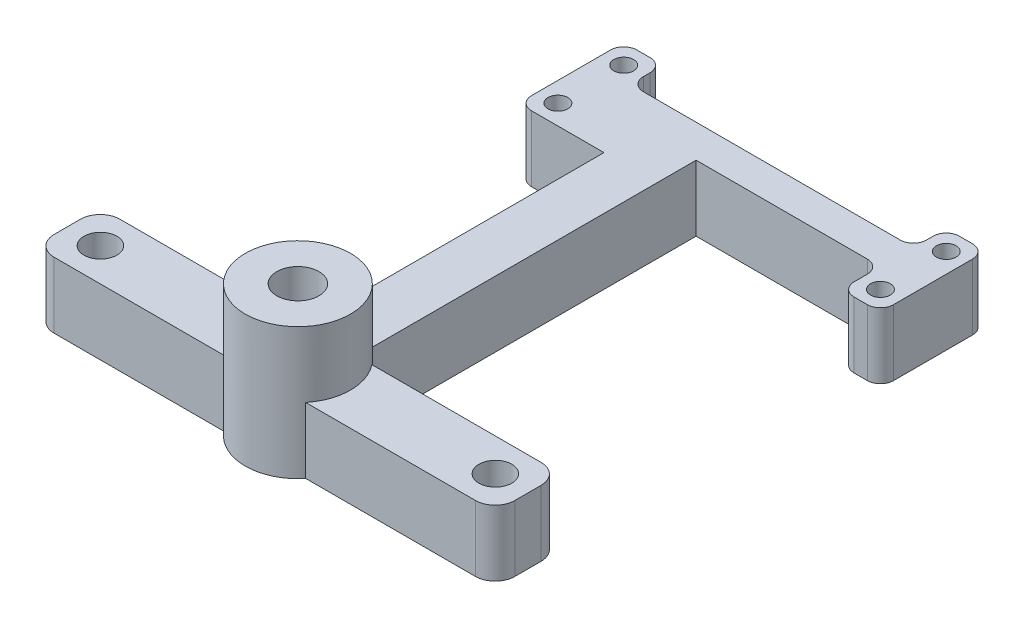
SolidWorks part; units mm, degrees
ref_plane "前视基准面" through (0, 0, 0) normal (0, 0, 1) x (1, 0, 0)
ref_plane "上视基准面" through (0, 0, 0) normal (0, 1, 0) x (1, 0, 0)
ref_plane "右视基准面" through (0, 0, 0) normal (1, 0, 0) x (0, 0, -1)
other "Configuration Table"
sketch "草图2" plane through (0, 0, 0) normal (0, 1, 0) x (1, 0, 0)
  line L1 (-4, -23) -> (4, -23)
  line L2 (-4, -23) -> (-4, -6)
  line L3 (-4, -6) -> (4, -6)
  line L4 (4, -23) -> (4, -6)
  line L5 (-4, -23) -> (4, -6) construction
  line L6 (-4, -6) -> (4, -23) construction
extrude "凸台-拉伸1" add sketch "草图2" along normal blind 10
sketch "草图4" plane through (0, 10, 0) normal (0, 1, 0) x (1, 0, 0)
  line L1 (-4, -23) -> (4, -23)
  line L4 (4, -23) -> (4, -61.5319)
  line L5 (-4, -23) -> (-4, -61.5319)
  line L11 (-4, -23) -> (4, -23) construction
  line L17 (-35, -61.5319) -> (-4, -61.5319)
  line L18 (-11.3444, -64.4193) -> (11.3444, -68.5807) construction
  line L20 (-11.3444, -84.9254) -> (11.3444, -48.0746) construction
  line L21 (-35, -61.5319) -> (-35, -71.5319)
  line L22 (-35, -71.5319) -> (35, -71.5319)
  line L23 (35, -61.5319) -> (35, -71.5319)
  line L24 (35, -61.5319) -> (4, -61.5319)
  circle A13 centre (0, -66.5) radius 3.2
  circle A14 centre (30, -66.5) radius 2.5
  circle A15 centre (-30, -66.5) radius 2.5
  point P0 (29.7411, -66.3231)
  point P11 (0, 0)
  point P12 (0, 0)
  point P13 (0, 0)
  point P37 (0, -66.5)
  point P38 (0, -66.5)
extrude "凸台-拉伸2" add sketch "草图4" against normal blind 10
sketch "草图6" plane through (0, 10, 0) normal (0, 1, 0) x (1, 0, 0)
  line L2 (-17, 0) -> (-17, -16)
  line L7 (38, 0) -> (38, -16)
  line L8 (-4, -6) -> (-4, -61.5319) construction
  line L9 (-4, -16) -> (-17, -16)
  line L10 (-11, 0) -> (-17, 0)
  line L11 (38, 0) -> (32, 0)
  line L12 (32, 0) -> (32, -5)
  line L13 (32, -5) -> (-11, -5)
  line L14 (-4, -6) -> (-4, -61.5319) construction
  line L15 (38, -16) -> (32, -16)
  line L16 (32, -16) -> (32, -10)
  line L17 (32, -10) -> (-4, -10)
  line L18 (-4, -10) -> (-4, -16)
  line L19 (-11, 0) -> (-11, -5)
  circle A0 centre (-14, -3) radius 1.5
  circle A1 centre (-14, -13) radius 1.5
  circle A2 centre (35, -3) radius 1.5
  circle A3 centre (35, -13) radius 1.5
extrude "凸台-拉伸3" add sketch "草图6" against normal blind 10
fillet "圆角6" radius 2 10 edges at (-11, 5, 5) (32, 5, 5) (32, 5, 0) (38, 5, 0) (38, 5, 16) (32, 5, 16) (32, 5, 10) (-11, 5, 0) (-17, 5, 16) (-17, 5, 0)
fillet "圆角7" radius 3 4 edges at (35, 5, 71.5319) (35, 5, 61.5319) (-35, 5, 71.5319) (-35, 5, 61.5319)
sketch "草图7" plane through (0, 10, 0) normal (0, 1, 0) x (1, 0, 0)
  circle A0 centre (0, -66.5) radius 3.2
  circle A1 centre (0, -66.5) radius 8
extrude "凸台-拉伸4" add sketch "草图7" along normal blind 10 and the other way blind 10
